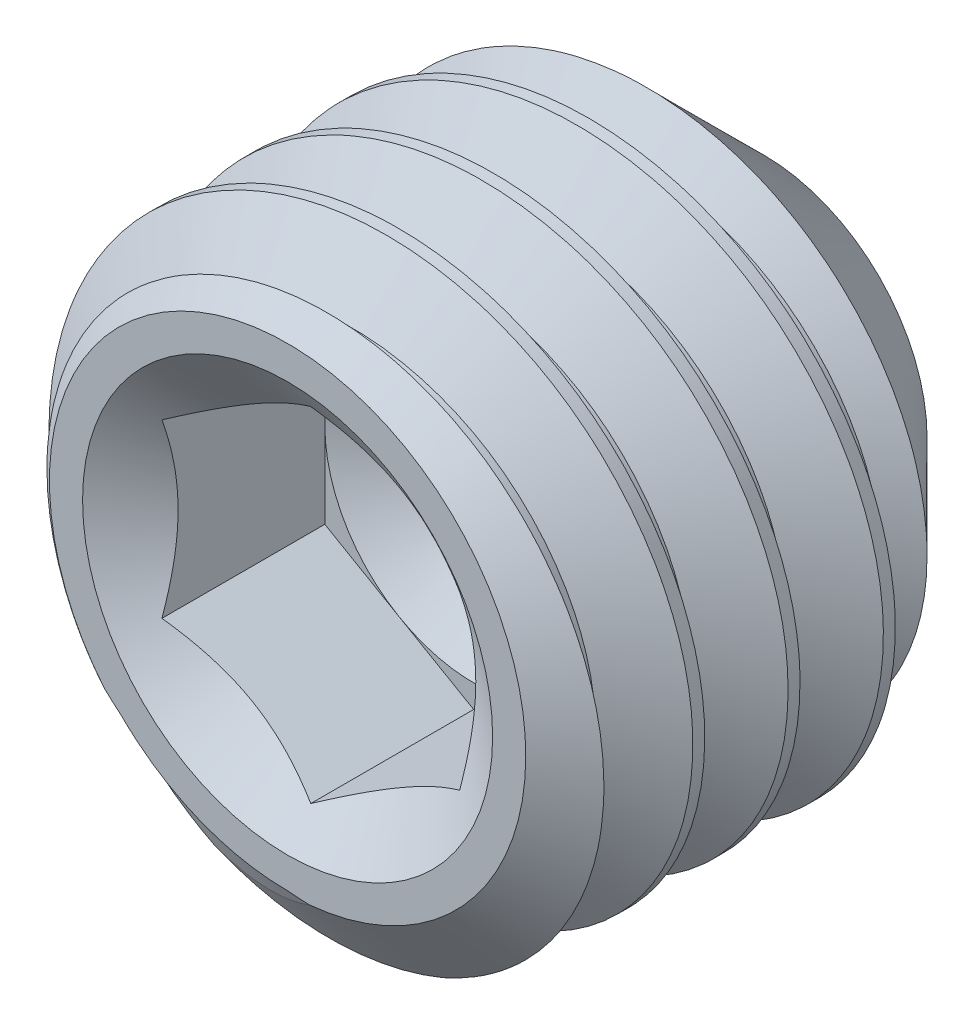
SolidWorks part; units mm, degrees
material "Stainless Steel (ferritic)"
ref_plane "Front" through (0, 0, 0) normal (0, 0, 1) x (1, 0, 0)
ref_plane "Top" through (0, 0, 0) normal (0, 1, 0) x (1, 0, 0)
ref_plane "Right" through (0, 0, 0) normal (1, 0, 0) x (0, 0, -1)
sketch "Sketch1" plane through (0, 0, 0) normal (1, 0, 0) x (0, 0, -1)
  line L0 (-1.5884, 0) -> (-1.5884, 2)
  line L1 (-1.5884, 2) -> (-1.2383, 2.5)
  line L2 (-1.2383, 2.5) -> (1.2815, 2.5)
  line L3 (1.2815, 2.5) -> (2.4116, 1.3699)
  line L4 (2.4116, 1.3699) -> (1.5884, 0)
  line L5 (1.5884, 0) -> (-1.5884, 0)
  line L6 (1.5884, 0) -> (2.4116, 0) construction
  line L7 (2.4116, 0) -> (2.4116, 1.3699) construction
  line L8 (2.4116, -1.3699) -> (1.5884, 0) construction
  line L9 (-1.2383, -2.5) -> (1.2815, -2.5) construction
  line L10 (0, 0) -> (0, -0.8) construction
  point P11 (-1.5884, 2.5)
  point P12 (-3.9685, -2.5)
  point P14 (2.4116, 2.5)
  dimension "Dia" = 5
  dimension "Length" = 4
  dimension "D3" = 35
  dimension "D5" = 118
  dimension "D6" = 45
  dimension "D7" = 4
  dimension "Pitch" = 0.8
  dimension "D1" = 5.25
revolve "Revolve1" add sketch "Sketch1" angle 360 about L6
sketch "Sketch2" plane through (0, 0, 1.5884) normal (0, 0, 1) x (1, 0, 0)
  line L1 (0, 1.4434) -> (-1.25, 0.7217)
  line L2 (-1.25, 0.7217) -> (-1.25, -0.7217)
  line L3 (-1.25, -0.7217) -> (0, -1.4434)
  line L4 (0, -1.4434) -> (1.25, -0.7217)
  line L5 (1.25, -0.7217) -> (1.25, 0.7217)
  line L6 (1.25, 0.7217) -> (0, 1.4434)
  circle A0 centre (0, 0) radius 1.25 construction
  circle A1 centre (0, 0) radius 2.5 construction
  dimension "Hex" = 2.5
extrude "Cut-Extrude1" cut sketch "Sketch2" against normal blind 1.5625
sketch "Sketch3" plane through (0, 0, 1.5884) normal (0, 0, 1) x (1, 0, 0)
  line L0 (0, 1.4434) -> (0, 2) construction
  circle A0 centre (0, 0) radius 1.7217
  point P5 (0, 1.7217)
  dimension "D1" = 0.2783
extrude "Cut-Extrude2" cut sketch "Sketch3" against normal through all draft 55
sketch "Sketch4" plane through (0, 0, 0.0259) normal (0, 0, 1) x (1, 0, 0)
  circle A0 centre (0, 0) radius 1.25 construction
  circle A1 centre (0, 0) radius 1.25
extrude "Cut-Extrude3" cut sketch "Sketch4" against normal through all draft 60
ref_plane "Plane1" through (0, 0, -2.4116) normal (0, 0, 1) x (1, 0, 0)
sketch "Sketch5" plane through (0, 0, -2.4116) normal (0, 0, 1) x (1, 0, 0)
  circle A0 centre (0, 0) radius 2.5 construction
  circle A1 centre (0, 0) radius 2.5
curve "Helix/Spiral1" pitch 0.8 height 4.8 radius 2.5 centre (0, 0, -2.4116) axis (0, 0, 1) start towards (0, 1, 0)
sketch "Sketch6" plane through (0, 0, 0) normal (1, 0, 0) x (0, 0, -1)
  line L0 (2.3616, 2.5866) -> (3.1616, 2.5866) construction
  line L1 (3.1616, 2.5866) -> (2.7616, 1.8938) construction
  line L2 (2.7616, 1.8938) -> (2.3616, 2.5866) construction
  line L3 (2.4116, 2.5) -> (3.1116, 2.5) construction
  line L4 (2.7116, 1.9804) -> (2.8116, 1.9804) construction
  line L5 (2.7616, 2.5) -> (2.7616, 2.5866) construction
  line L7 (2.7616, 1.9804) -> (2.7616, 1.8938) construction
  line L8 (2.7616, 2.5433) -> (2.3866, 2.5433) construction
  line L9 (2.7116, 1.9804) -> (2.3866, 2.5433)
  line L10 (2.3866, 2.5433) -> (3.1366, 2.5433)
  line L11 (3.1366, 2.5433) -> (2.8116, 1.9804)
  line L12 (2.8116, 1.9804) -> (2.7116, 1.9804)
  dimension "D1" = 0.8
  dimension "D2" = 0.1
sweep "Cut-Sweep1" cut profiles "Sketch6" path "Helix/Spiral1"
ref_axis "Center Axis 1" through (0, 0, 3.3456) along (0, 0, -1)
ref_plane "Contact Plane 1" through (0, 0, 1.5884) normal (0, 0, 1) x (1, 0, 0)
ref_plane "Contact Plane 2" through (0, 0, -2.4116) normal (0, 0, 1) x (1, 0, 0)
equation "\"D7@Sketch1\" = \"Dia@Sketch1\" * .8"
equation "\"hex Depth@Cut-Extrude1\" = \"Hex@Sketch2\" * .625"
equation "\"D3@Helix/Spiral1\" = \"Length@Sketch1\" + \"Pitch@Sketch1\""
equation "\"D4@Helix/Spiral1\" = \"Pitch@Sketch1\""
equation "\"D1@Sketch6\" = \"Pitch@Sketch1\""
equation "\"D2@Sketch6\"=\"D1@Sketch6\"/8"
